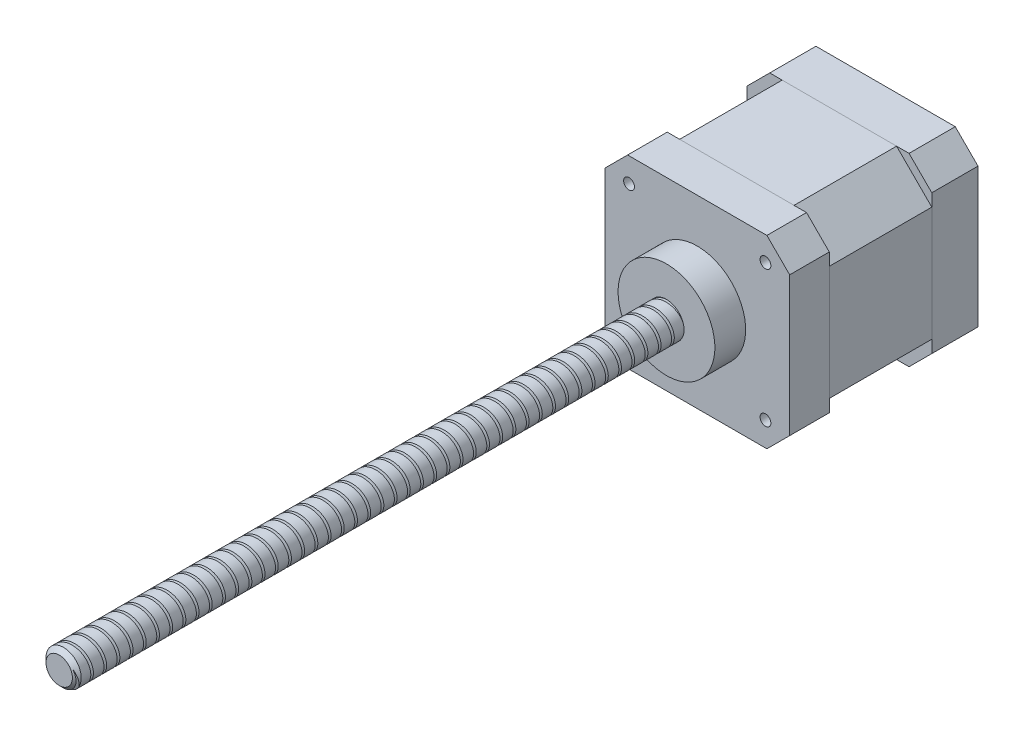
SolidWorks part; units mm, degrees
ref_plane "Front Plane" through (0, 0, 0) normal (0, 0, 1) x (1, 0, 0)
ref_plane "Top Plane" through (0, 0, 0) normal (0, 1, 0) x (1, 0, 0)
ref_plane "Right Plane" through (0, 0, 0) normal (1, 0, 0) x (0, 0, -1)
ref_plane "Plane1" through (0, 0, 0) normal (0, 0, -1) x (-1, 0, 0)
sketch "Sketch1" plane through (0, 0, 0) normal (0, 0, -1) x (-1, 0, 0)
  line L0 (-15.8284, 21) -> (-21, 15.8284)
  line L1 (-21, 15.8284) -> (-21, -15.8284)
  line L2 (-21, -15.8284) -> (-15.8284, -21)
  line L3 (-15.8284, -21) -> (15.8284, -21)
  line L4 (15.8284, -21) -> (21, -15.8284)
  line L5 (21, -15.8284) -> (21, 15.8284)
  line L6 (21, 15.8284) -> (15.8284, 21)
  line L7 (15.8284, 21) -> (-15.8284, 21)
extrude "Boss-Extrude1" add sketch "Sketch1" against normal blind 10.5
sketch "Sketch2" plane through (0, 0, 10.5) normal (0, 0, 1) x (1, 0, 0)
  line L0 (13, -21) -> (-13, -21)
  line L1 (-13, -21) -> (-21, -13)
  line L2 (-21, -13) -> (-21, 13)
  line L3 (-21, 13) -> (-13, 21)
  line L4 (-13, 21) -> (13, 21)
  line L5 (13, 21) -> (21, 13)
  line L6 (21, 13) -> (21, -13)
  line L7 (21, -13) -> (13, -21)
extrude "Boss-Extrude2" add sketch "Sketch2" along normal blind 23.3
sketch "Sketch3" plane through (0, 0, 33.8) normal (0, 0, 1) x (1, 0, 0)
  line L0 (15.8284, 21) -> (21, 15.8284)
  line L1 (21, 15.8284) -> (21, -15.8284)
  line L2 (21, -15.8284) -> (15.8284, -21)
  line L3 (15.8284, -21) -> (-15.8284, -21)
  line L4 (-15.8284, -21) -> (-21, -15.8284)
  line L5 (-21, -15.8284) -> (-21, 15.8284)
  line L6 (-21, 15.8284) -> (-15.8284, 21)
  line L7 (-15.8284, 21) -> (15.8284, 21)
extrude "Boss-Extrude3" add sketch "Sketch3" along normal blind 9
ref_plane "Plane2" through (0, 0, 3.65) normal (0, 0, 1) x (1, 0, 0)
ref_plane "Plane3" through (0, 0, 4.95) normal (0, 0, 1) x (1, 0, 0)
ref_plane "Plane4" through (0, 0, 0) normal (0, -1, 0) x (1, 0, 0)
sketch "Sketch8" plane through (0, 0, 0) normal (0, -1, 0) x (1, 0, 0)
  line L0 (4, 187.8) -> (0, 187.8)
  line L1 (0, 187.8) -> (0, 42.8)
  line L2 (0, 42.8) -> (11, 42.8)
  line L3 (11, 42.8) -> (11, 49.8)
  line L4 (11, 49.8) -> (4, 49.8)
  line L5 (4, 49.8) -> (4, 187.8)
  line L6 (0, 187.8) -> (0, 42.8) construction
  line L7 (-15.8284, 42.8) -> (15.8284, 42.8) construction
  dimension "D1" = 145
  dimension "D2" = 7
  dimension "D3" = 4
  dimension "D4" = 11
revolve "Revolve5" add sketch "Sketch8" angle 360 about L6
hole_wizard "Hole1" positions "Sketch10" profile "Sketch9" legacy
sketch "Sketch10" plane through (0, 0, 42.8) normal (0, 0, 1) x (1, 0, 0)
  point P0 (-15.5, 15.5)
sketch "Sketch9" plane through (-15.5, 15.5, 42.8) normal (1, 0, 0) x (0, -1, 0)
  line L0 (0, 0) -> (0, 5)
  line L1 (0, 5) -> (1.2295, 5)
  line L2 (1.2295, 5) -> (1.2295, 0)
  line L3 (1.2295, 0) -> (0, 0)
  line L4 (0, 110) -> (0, -10) construction
  dimension "Diameter" = 2.459
  dimension "Depth" = 5
hole_wizard "Hole2" positions "Sketch12" profile "Sketch11" legacy
sketch "Sketch12" plane through (0, 0, 42.8) normal (0, 0, 1) x (1, 0, 0)
  point P0 (-15.5, -15.5)
sketch "Sketch11" plane through (-15.5, -15.5, 42.8) normal (1, 0, 0) x (0, -1, 0)
  line L0 (0, 0) -> (0, 5)
  line L1 (0, 5) -> (1.2295, 5)
  line L2 (1.2295, 5) -> (1.2295, 0)
  line L3 (1.2295, 0) -> (0, 0)
  line L4 (0, 110) -> (0, -10) construction
  dimension "Diameter" = 2.459
  dimension "Depth" = 5
hole_wizard "Hole3" positions "Sketch14" profile "Sketch13" legacy
sketch "Sketch14" plane through (0, 0, 42.8) normal (0, 0, 1) x (1, 0, 0)
  point P0 (15.5, 15.5)
sketch "Sketch13" plane through (15.5, 15.5, 42.8) normal (1, 0, 0) x (0, -1, 0)
  line L0 (0, 0) -> (0, 5)
  line L1 (0, 5) -> (1.2295, 5)
  line L2 (1.2295, 5) -> (1.2295, 0)
  line L3 (1.2295, 0) -> (0, 0)
  line L4 (0, 110) -> (0, -10) construction
  dimension "Diameter" = 2.459
  dimension "Depth" = 5
hole_wizard "Hole4" positions "Sketch16" profile "Sketch15" legacy
sketch "Sketch16" plane through (0, 0, 42.8) normal (0, 0, 1) x (1, 0, 0)
  point P0 (15.5, -15.5)
sketch "Sketch15" plane through (15.5, -15.5, 42.8) normal (1, 0, 0) x (0, -1, 0)
  line L0 (0, 0) -> (0, 5)
  line L1 (0, 5) -> (1.2295, 5)
  line L2 (1.2295, 5) -> (1.2295, 0)
  line L3 (1.2295, 0) -> (0, 0)
  line L4 (0, 110) -> (0, -10) construction
  dimension "Diameter" = 2.459
  dimension "Depth" = 5
sketch "Sketch17" plane through (21, 0, 0) normal (1, 0, 0) x (0, 0, -1)
  line L0 (-33.8, -34.1726) -> (-33.8, 24.5624)
  line L1 (-10.5, 27.343) -> (-10.5, -30.7725)
  line L2 (-10.5, 21) -> (-10.5, 15.8284) construction
  line L3 (-33.8, 13) -> (-33.8, 21) construction
split line "Split Line1"
sketch "Croquis1" plane through (0, 0, 0) normal (1, 0, 0) x (0, 0, -1)
  line L0 (-188.4, 4) -> (-188.1, 3.2)
  line L1 (-188.1, 3.2) -> (-187.8, 4)
  line L2 (-187.8, 4) -> (-188.4, 4)
  point P7 (-188.1, 4)
  dimension "D1" = 0.6
  dimension "D2" = 0.8
sketch "Croquis2" plane through (0, 0, 187.8) normal (0, 0, 1) x (1, 0, 0)
  circle A0 centre (0, 0) radius 4
curve "Hélice/Espiral1" pitch 3 height 240 turns 80
sweep "Cortar-Barrer1" cut profiles "Croquis1" path "Hélice/Espiral1"
chamfer "Chaflán1" distance 1 angle 45 1 edges at (-2.3664, -3.2249, 187.8)
